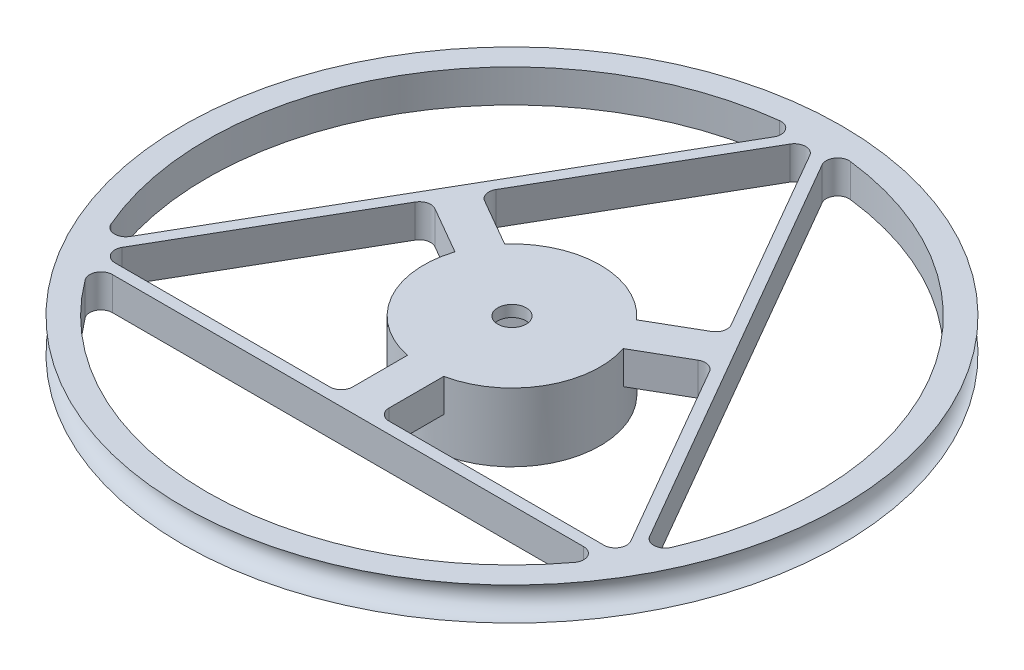
SolidWorks part; units mm, degrees
ref_plane "Front Plane" through (0, 0, 0) normal (0, 0, 1) x (1, 0, 0)
ref_plane "Top Plane" through (0, 0, 0) normal (0, 1, 0) x (1, 0, 0)
ref_plane "Right Plane" through (0, 0, 0) normal (1, 0, 0) x (0, 0, -1)
sketch "Sketch1" plane through (0, 0, 0) normal (0, 1, 0) x (1, 0, 0)
  line L0 (-1.0999, 32.1463) -> (-13.1159, 11.3339)
  line L1 (-27.2896, -17.0256) -> (-3.302, -17.0256)
  line L2 (28.3894, -15.1206) -> (16.3956, 5.6532)
  line L3 (-2.6935, 31.9261) -> (-28.9955, -13.6304)
  line L4 (2.6935, 31.9261) -> (28.9955, -13.6304)
  line L5 (-26.3021, -18.2956) -> (26.3021, -18.2956)
  line L6 (3.302, -17.0256) -> (27.2896, -17.0256)
  line L7 (-12.651, 9.5991) -> (-7.3683, 6.5491)
  line L8 (-14.683, 6.0795) -> (-9.3841, 3.0202)
  line L9 (12.6288, 9.6376) -> (7.338, 6.583)
  line L10 (9.37, 3.0634) -> (14.6608, 6.1181)
  line L11 (13.0936, 11.3724) -> (1.0999, 32.1463)
  line L12 (-2.032, -9.6464) -> (-2.032, -15.7556)
  line L13 (2.032, -15.7556) -> (2.032, -9.6464)
  line L14 (-16.4179, 5.6147) -> (-28.3894, -15.1206)
  circle A0 centre (0, 0) radius 36.7851
  arc A1 (-3.9403, 33.8225) -> (-31.2613, -13.4989) centre (0, 0) ccw
  arc A2 (-27.321, -20.3236) -> (27.321, -20.3236) centre (0, 0) ccw
  arc A3 (31.2613, -13.4989) -> (3.9403, 33.8225) centre (0, 0) ccw
  arc A4 (27.321, -20.3236) -> (26.3021, -18.2956) centre (26.3021, -19.5656) ccw
  arc A5 (27.2896, -17.0256) -> (28.3894, -15.1206) centre (27.2896, -15.7556) ccw
  arc A6 (28.9955, -13.6304) -> (31.2613, -13.4989) centre (30.0954, -12.9954) ccw
  arc A7 (-31.2613, -13.4989) -> (-28.9955, -13.6304) centre (-30.0954, -12.9954) ccw
  arc A8 (-27.321, -20.3236) -> (-26.3021, -18.2956) centre (-26.3021, -19.5656) cw
  arc A9 (-27.2896, -17.0256) -> (-28.3894, -15.1206) centre (-27.2896, -15.7556) cw
  arc A10 (1.0999, 32.1463) -> (-1.0999, 32.1463) centre (0, 31.5113) ccw
  arc A11 (2.6935, 31.9261) -> (3.9403, 33.8225) centre (3.7933, 32.5611) cw
  arc A12 (-2.6935, 31.9261) -> (-3.9403, 33.8225) centre (-3.7933, 32.5611) ccw
  arc A13 (-7.3683, 6.5491) -> (-9.3841, 3.0202) centre (0, 0) ccw
  arc A14 (-2.032, -9.6464) -> (2.032, -9.6464) centre (0, 0) ccw
  arc A15 (9.37, 3.0634) -> (7.338, 6.583) centre (0, 0) ccw
  arc A16 (3.302, -17.0256) -> (2.032, -15.7556) centre (3.302, -15.7556) cw
  arc A17 (16.3956, 5.6532) -> (14.6608, 6.1181) centre (15.2958, 5.0182) ccw
  arc A18 (13.0936, 11.3724) -> (12.6288, 9.6376) centre (11.9938, 10.7374) cw
  arc A19 (-12.651, 9.5991) -> (-13.1159, 11.3339) centre (-12.016, 10.6989) cw
  arc A20 (-14.683, 6.0795) -> (-16.4179, 5.6147) centre (-15.318, 4.9797) ccw
  arc A21 (-3.302, -17.0256) -> (-2.032, -15.7556) centre (-3.302, -15.7556) ccw
  point P12 (28.7186, -18.2956)
  point P17 (29.4893, -17.0256)
  point P20 (30.2038, -15.7232)
  point P25 (-28.7186, -18.2956)
  point P28 (-29.4893, -17.0256)
  point P31 (0, 34.0513)
  point P47 (2.032, -17.0256)
  point P55 (13.7286, 10.2726)
  point P60 (-15.7829, 6.7145)
  dimension "D1" = 1.27
  dimension "D4" = 1.27
  dimension "D5" = 4.064
  dimension "D6" = 1.27
  dimension "D8" = 1.27
  dimension "D2" = 1.27
  dimension "D3" = 1.27
  dimension "D7" = 4.064
  dimension "D9" = 4.064
extrude "Boss-Extrude1" add sketch "Sketch1" along normal blind 3.683
sketch "Sketch2" plane through (0, 0, 0) normal (0, 0, 1) x (1, 0, 0)
  line L1 (36.7851, 0) -> (36.7851, 3.683) construction
  line L2 (0, 0) -> (0, 17.4834) construction
  circle A0 centre (36.7851, 1.8415) radius 1.8415
sketch "Sketch4" plane through (0, 0, 0) normal (1, 0, 0) x (0, 0, -1)
  line L0 (0, 1.1871) -> (0, 9.1244) construction
  line L1 (0, 3.683) -> (0, 0) construction
  line L2 (0, 9.1244) -> (0, -8.0635) construction
ref_axis "Axis1" through (0, 9.1244, 0) along (0, -1, 0)
revolve "Cut-Revolve2" cut sketch "Sketch2" angle 360 about L2
sketch "Sketch5" plane through (0, 3.683, 0) normal (0, 1, 0) x (1, 0, 0)
  circle A0 centre (0, 0) radius 9.8581
extrude "Boss-Extrude2" add sketch "Sketch5" against normal blind 7.62
sketch "Sketch6" plane through (0, -3.937, 0) normal (0, -1, 0) x (1, 0, 0)
  circle A0 centre (0, 0) radius 1.5875
extrude "Cut-Extrude1" cut sketch "Sketch6" against normal through all
sketch "Sketch8" plane through (0, -3.937, 0) normal (0, -1, 0) x (1, 0, 0)
  line L1 (0, 6.35) -> (-5.4993, 3.175)
  line L2 (-5.4993, 3.175) -> (-5.4993, -3.175)
  line L3 (-5.4993, -3.175) -> (0, -6.35)
  line L4 (0, -6.35) -> (5.4993, -3.175)
  line L5 (5.4993, -3.175) -> (5.4993, 3.175)
  line L6 (5.4993, 3.175) -> (0, 6.35)
  circle A0 centre (0, 0) radius 5.4993 construction
  dimension "D1" = 6.35
extrude "Cut-Extrude3" cut sketch "Sketch8" against normal blind 6.35
